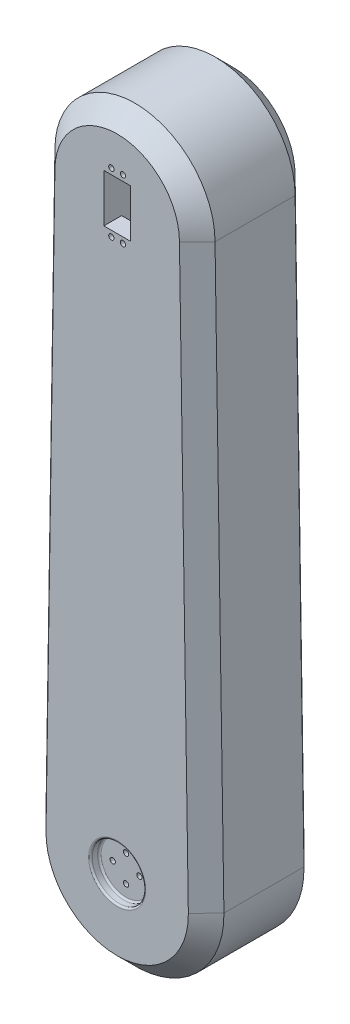
SolidWorks part; units mm, degrees
ref_plane "Front Plane" through (0, 0, 0) normal (0, 0, 1) x (1, 0, 0)
ref_plane "Top Plane" through (0, 0, 0) normal (0, 1, 0) x (1, 0, 0)
ref_plane "Right Plane" through (0, 0, 0) normal (1, 0, 0) x (0, 0, -1)
sketch "Sketch1" plane through (0, 0, 0) normal (0, 0, 1) x (1, 0, 0)
  line L0 (0, 0) -> (0, 1270.6213) construction
  line L1 (45, 325) -> (49.9941, 0.7701)
  line L2 (-45, 325) -> (-49.9941, 0.7701)
  arc A0 (-49.9941, 0.7701) -> (49.9941, 0.7701) centre (0, 0) ccw
  arc A1 (45, 325) -> (-45, 325) centre (0, 325) ccw
  dimension "D1" = 100
  dimension "D2" = 90
  dimension "D3" = 325
extrude "Boss-Extrude1" add sketch "Sketch1" along normal blind 65
sketch "Sketch2" plane through (0, 0, 65) normal (0, 0, 1) x (1, 0, 0)
  circle A0 centre (0, 0) radius 15
  dimension "D1" = 30
extrude "Cut-Extrude1" cut sketch "Sketch2" against normal blind 5
sketch "Sketch3" plane through (0, 0, 60) normal (0, 0, 1) x (1, 0, 0)
  line L0 (-15, 0) -> (15, 0) construction
  line L1 (0, -15) -> (0, 19.4745) construction
  circle A0 centre (0, 0) radius 15 construction
  circle A1 centre (0, 0) radius 15 construction
  circle A2 centre (0, 7.5) radius 1.5
  circle A3 centre (7.5, 0) radius 1.5
  circle A4 centre (0, -7.5) radius 1.5
  circle A5 centre (-7.5, 0) radius 1.5
  point P10 (0, 0)
  point P11 (0, 0)
  point P22 (0, 0)
  dimension "D1" = 3
  dimension "D2" = 7.5
  dimension "D3" = 4
extrude "Cut-Extrude2" cut sketch "Sketch3" against normal blind 7.5
chamfer "Chamfer1" distance 10 8 edges at (0, -50, 0) (-47.497, 162.885, 0) (0, 370, 0) (47.497, 162.885, 0) (0, -50, 65) (-47.497, 162.885, 65) (0, 370, 65) (47.497, 162.885, 65)
fillet "Fillet1" radius 1 2 edges at (15, 0, 65) (15, 0, 60)
sketch "Sketch4" plane through (0, 0, 0) normal (0, 0, -1) x (-1, 0, 0)
  line L0 (0, 370) -> (0, -62.6857) construction
  line L2 (-7.5, 345) -> (7.5, 345)
  line L3 (-7.5, 345) -> (-7.5, 305)
  line L4 (-7.5, 305) -> (7.5, 305)
  line L5 (7.5, 345) -> (7.5, 305)
  line L6 (-7.5, 345) -> (7.5, 305) construction
  line L7 (-7.5, 305) -> (7.5, 345) construction
  arc A0 (45, 325) -> (-45, 325) centre (0, 325) ccw construction
  point P6 (0, 325)
  dimension "D1" = 40
  dimension "D2" = 15
extrude "Cut-Extrude3" cut sketch "Sketch4" against normal offset from surface (55 mm away) 10 up to face at (16, 0, 65)
sketch "Sketch5" plane through (0, 0, 55) normal (0, 0, -1) x (-1, 0, 0)
  line L0 (7.5, 305) -> (7.5, 345) construction
  line L1 (-7.5, 345) -> (7.5, 345)
  line L2 (-7.5, 345) -> (-7.5, 338.5)
  line L3 (-7.5, 338.5) -> (7.5, 338.5)
  line L4 (7.5, 345) -> (7.5, 338.5)
  line L5 (-7.5, 345) -> (-7.5, 305) construction
  line L6 (7.5, 305) -> (-7.5, 305)
  line L7 (7.5, 305) -> (7.5, 311.5)
  line L8 (7.5, 311.5) -> (-7.5, 311.5)
  line L9 (-7.5, 305) -> (-7.5, 311.5)
  line L10 (-7.5, 325) -> (7.5, 325) construction
  line L11 (-7.5, 345) -> (-7.5, 305) construction
  line L12 (7.5, 305) -> (7.5, 345) construction
  line L13 (0, 345) -> (0.0001, 345) construction
  line L14 (0, 426.2841) -> (0, 223.7159) construction
  line L15 (-7.5, 338.5) -> (-7.5, 311.5)
  line L16 (7.5, 338.5) -> (7.5, 311.5)
  circle A0 centre (-3.25, 341.75) radius 1.5
  circle A1 centre (3.25, 341.75) radius 1.5
  circle A2 centre (3.25, 308.25) radius 1.5
  circle A3 centre (-3.25, 308.25) radius 1.5
  point P27 (0, 325)
  line M12 (7.5, 305) -> (7.5, 345)
  line M14 (-7.5, 345) -> (-7.5, 305)
  dimension "D3" = 3
  dimension "D1" = 6.5
  dimension "D2" = 6.5
  dimension "D4" = 3.25
  dimension "D5" = 3.25
extrude "Cut-Extrude5" cut sketch "Sketch5" against normal through all contours L8 L3 M12 M14 | A0 | A1 | A3 | A2 region at (0, 325, 55) region at (3.25, 341.75, 55) region at (-3.25, 341.75, 55) region at (-3.25, 308.25, 55) region at (3.25, 308.25, 55)
sketch "Sketch6" plane through (0, 0, 65) normal (0, 0, 1) x (1, 0, 0)
  line L0 (0, 338.5) -> (0, 311.5) construction
  line L1 (7.5, 338.5) -> (-7.5, 338.5) construction
  line L2 (-7.5, 311.5) -> (7.5, 311.5) construction
  circle A0 centre (0, 325) radius 3.75 construction
  dimension "D1" = 7.5
